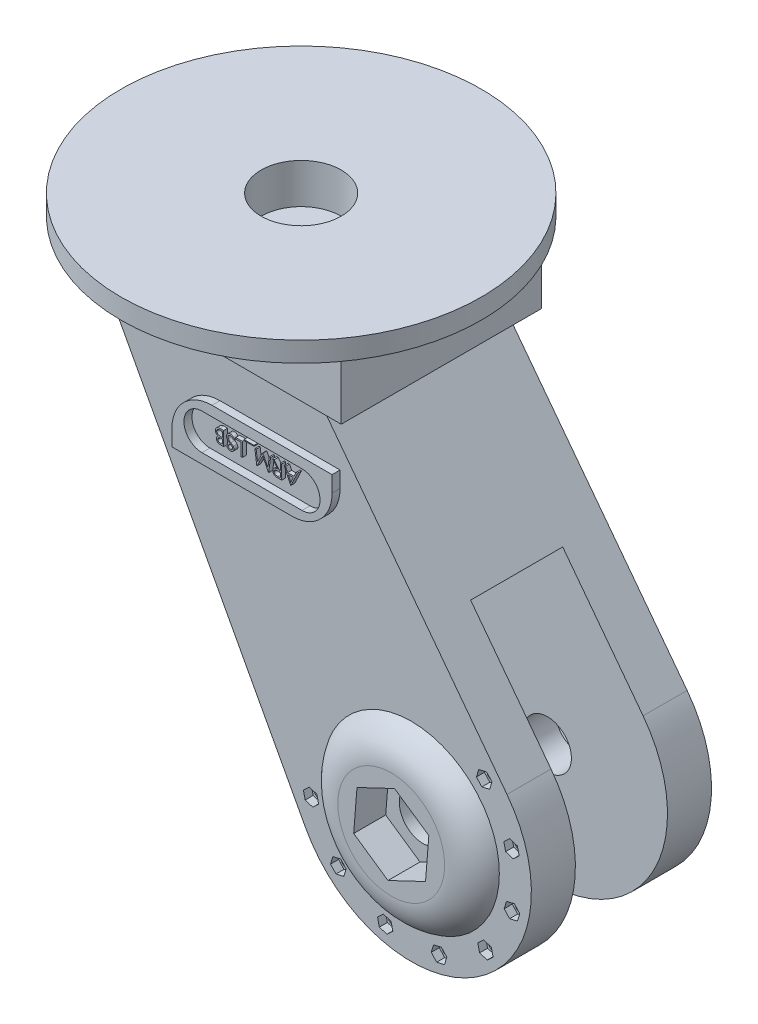
SolidWorks part; units mm, degrees
ref_plane "Ön Düzlem" through (0, 0, 0) normal (0, 0, 1) x (1, 0, 0)
ref_plane "Üst Düzlem" through (0, 0, 0) normal (0, 1, 0) x (1, 0, 0)
ref_plane "Sağ Düzlem" through (0, 0, 0) normal (1, 0, 0) x (0, 0, -1)
sketch "Sketch1" plane through (0, 0, 0) normal (0, 1, 0) x (1, 0, 0)
  circle A0 centre (0, 0) radius 45
  dimension "D1" = 90
extrude "Boss-Extrude1" add sketch "Sketch1" along normal blind 5
sketch "Sketch2" plane through (0, 5, 0) normal (0, 1, 0) x (1, 0, 0)
  line L1 (-35, 25) -> (35, 25)
  line L2 (-35, 25) -> (-35, -25)
  line L3 (-35, -25) -> (35, -25)
  line L4 (35, 25) -> (35, -25)
  line L5 (-35, 25) -> (35, -25) construction
  line L6 (-35, -25) -> (35, 25) construction
  point P0 (0, 0)
  dimension "D1" = 70
  dimension "D2" = 50
extrude "Boss-Extrude2" add sketch "Sketch2" along normal blind 15
sketch "Sketch3" plane through (0, 0, 0) normal (0, 0, 1) x (1, 0, 0)
  line L0 (-45, 0) -> (45, 0) construction
  line L1 (-27, 20) -> (-73.907, 81.8767)
  line L2 (-35, 20) -> (35, 20) construction
  line L3 (-27, 20) -> (27, 20)
  line L4 (27, 20) -> (-23.5684, 114.1904)
  arc A0 (-23.5684, 114.1904) -> (-73.907, 81.8767) centre (-50, 100) ccw
  dimension "D1" = 60
  dimension "D2" = 100
  dimension "D3" = 50
  dimension "D4" = 8
  dimension "D5" = 8
extrude "Boss-Extrude3" add sketch "Sketch3" along normal mid plane 45
sketch "Sketch4" plane through (0, 0, 22.5) normal (0, 0, 1) x (1, 0, 0)
  circle A0 centre (-50, 100) radius 22
  dimension "D1" = 44
extrude "Boss-Extrude4" add sketch "Sketch4" along normal blind 5
fillet "Fillet1" radius 10 1 edges at (-28, 100, 27.5)
sketch "Sketch5" plane through (0, 0, 27.5) normal (0, 0, 1) x (1, 0, 0)
  line L1 (-50.8234, 89.6404) -> (-41.44, 94.1071)
  line L2 (-41.44, 94.1071) -> (-40.6166, 104.4667)
  line L3 (-40.6166, 104.4667) -> (-49.1766, 110.3596)
  line L4 (-49.1766, 110.3596) -> (-58.56, 105.8929)
  line L5 (-58.56, 105.8929) -> (-59.3834, 95.5333)
  line L6 (-59.3834, 95.5333) -> (-50.8234, 89.6404)
  circle A0 centre (-50, 100) radius 9 construction
  dimension "D1" = 18
extrude "Cut-Extrude1" cut sketch "Sketch5" against normal blind 8
sketch "Sketch6" plane through (29.294, 15.7272, 0) normal (0.8811, 0.473, 0) x (0, 0, -1)
  line L0 (-22.5, 111.7562) -> (22.5, 111.7562) construction
  line L1 (-11.5, 149.2562) -> (11.5, 149.2562)
  line L2 (-11.5, 149.2562) -> (-11.5, 74.2562)
  line L3 (-11.5, 74.2562) -> (11.5, 74.2562)
  line L4 (11.5, 149.2562) -> (11.5, 74.2562)
  line L5 (-11.5, 149.2562) -> (11.5, 74.2562) construction
  line L6 (-11.5, 74.2562) -> (11.5, 149.2562) construction
  point P0 (0, 111.7562)
  dimension "D1" = 23
  dimension "D2" = 75
extrude "Cut-Extrude2" cut sketch "Sketch6" against normal blind 110
sketch "Sketch7" plane through (0, 0, 19.5) normal (0, 0, 1) x (1, 0, 0)
  circle A0 centre (-50, 100) radius 6
  dimension "D1" = 12
extrude "Cut-Extrude4" cut sketch "Sketch7" against normal blind 20
sketch "Sketch8" plane through (0, 0, 22.5) normal (0, 0, 1) x (1, 0, 0)
  line L1 (-30.4213, 117.0633) -> (-29.8341, 118.9751)
  line L2 (-29.8341, 118.9751) -> (-31.1963, 120.4396)
  line L3 (-31.1963, 120.4396) -> (-33.1456, 119.9922)
  line L4 (-33.1456, 119.9922) -> (-33.7328, 118.0803)
  line L5 (-33.7328, 118.0803) -> (-32.3706, 116.6159)
  line L6 (-32.3706, 116.6159) -> (-30.4213, 117.0633)
  circle A0 centre (-31.7835, 118.5277) radius 1.7321 construction
  circle A1 centre (-50, 100) radius 22 construction
  point P1 (-34.7311, 115.8386)
  dimension "D1" = 4
  dimension "D2" = 3.99
extrude "Cut-Extrude5" cut sketch "Sketch8" against normal blind 2
sketch "Sketch9" plane through (0, 0, 20.5) normal (0, 0, 1) x (1, 0, 0)
  circle A0 centre (-31.7835, 118.5277) radius 1.25
  dimension "D1" = 2.5
extrude "Cut-Extrude6" cut sketch "Sketch9" against normal blind 1
pattern_circular "CirPattern1" count 12 over 360 about axis through (-50, 100, 22.5) along (0, 0, 1) skipping 7, 8, 9, 10 of "Cut-Extrude5", "Cut-Extrude6"
sketch "Sketch10" plane through (0, 0, 22.5) normal (0, 0, 1) x (1, 0, 0)
  line L0 (-50, 100) -> (0, 20) construction
  line L1 (-27, 20) -> (27, 20) construction
  line L3 (-32.2133, 46.5413) -> (7.7867, 46.5413)
  line L4 (-32.2133, 46.5413) -> (-32.2133, 32.5413)
  line L5 (-32.2133, 32.5413) -> (7.7867, 32.5413)
  line L6 (7.7867, 46.5413) -> (7.7867, 32.5413)
  line L7 (-32.2133, 46.5413) -> (7.7867, 32.5413) construction
  line L8 (-32.2133, 32.5413) -> (7.7867, 46.5413) construction
  point P5 (-12.2133, 39.5413)
  dimension "D1" = 14
  dimension "D2" = 40
extrude "Boss-Extrude5" add sketch "Sketch10" along normal blind 2
sketch "Sketch11" plane through (0, 0, 24.5) normal (0, 0, 1) x (1, 0, 0)
  line L0 (-24.7133, 39.5413) -> (0.2867, 39.5413) construction
  line L1 (-24.7133, 44.0413) -> (0.2867, 44.0413)
  line L2 (-24.7133, 35.0413) -> (0.2867, 35.0413)
  line L3 (-32.2133, 46.5413) -> (-32.2133, 32.5413) construction
  line L4 (7.7867, 32.5413) -> (7.7867, 46.5413) construction
  line L5 (7.7867, 46.5413) -> (-32.2133, 46.5413) construction
  line L6 (-32.2133, 32.5413) -> (7.7867, 32.5413) construction
  arc A0 (-24.7133, 44.0413) -> (-24.7133, 35.0413) centre (-24.7133, 39.5413) ccw
  arc A1 (0.2867, 35.0413) -> (0.2867, 44.0413) centre (0.2867, 39.5413) ccw
  point P2 (-12.2133, 39.5413)
  point P7 (-32.2133, 39.5413)
  point P10 (7.7867, 39.5413)
  dimension "D1" = 7.5
  dimension "D2" = 7.5
  dimension "D3" = 2.5
  dimension "D4" = 2.5
extrude "Cut-Extrude7" cut sketch "Sketch11" against normal blind 2
fillet "Fillet2" radius 10 2 edges at (7.7867, 32.5413, 23.5) (-32.2133, 46.5413, 23.5)
ref_plane "Plane1" through (0, 0, 0) normal (0, 0, -1) x (-1, 0, 0)
mirror "Mirror1" about plane through (0, 0, 0) normal (0, 0, -1) of "Fillet2", "Cut-Extrude7", "Boss-Extrude5", "CirPattern1", "Cut-Extrude6", "Cut-Extrude5", "Cut-Extrude2", "Cut-Extrude4", "Cut-Extrude1", "Fillet1", "Boss-Extrude4"
sketch "Sketch14" plane through (0, 0, -22.5) normal (0, 0, -1) x (-1, 0, 0)
  text T0 "ARM ROBOT"
extrude "Boss-Extrude6" add sketch "Sketch14" along normal blind 1
sketch "Sketch15" plane through (0, 0, 22.5) normal (0, 0, 1) x (1, 0, 0)
  line L0 (0.2867, 44.0413) -> (-24.7133, 44.0413) construction
  text T0 "ARM_LSB"
  dimension "D1" = 6.5
extrude "Boss-Extrude7" add sketch "Sketch15" along normal blind 1
sketch "Sketch16" plane through (35, 0, 0) normal (1, 0, 0) x (0, 0, -1)
  line L0 (-18.5, 12.5) -> (18.5, 12.5) construction
  line L1 (-18.5, 16.5) -> (18.5, 16.5)
  line L2 (-18.5, 8.5) -> (18.5, 8.5)
  line L3 (-25, 20) -> (-25, 5) construction
  line L4 (25, 20) -> (25, 5) construction
  line L5 (-22.5, 20) -> (22.5, 20) construction
  line L6 (-25, 5) -> (25, 5) construction
  arc A0 (-18.5, 16.5) -> (-18.5, 8.5) centre (-18.5, 12.5) ccw
  arc A1 (18.5, 8.5) -> (18.5, 16.5) centre (18.5, 12.5) ccw
  point P2 (0, 12.5)
  point P7 (-25, 12.5)
  point P10 (25, 12.5)
  dimension "D1" = 6.5
  dimension "D2" = 6.5
  dimension "D3" = 3.5
  dimension "D4" = 3.5
extrude "Cut-Extrude8" cut sketch "Sketch16" against normal blind 1
sketch "Sketch17" plane through (34, 0, 0) normal (1, 0, 0) x (0, 0, -1)
  text T0 "DO NOT TOUCH"
extrude "Boss-Extrude8" add sketch "Sketch17" along normal blind 1
sketch "Sketch18" plane through (0, 0, 0) normal (0, -1, 0) x (1, 0, 0)
  circle A0 centre (0, 0) radius 10
  dimension "D1" = 20
extrude "Cut-Extrude9" cut sketch "Sketch18" against normal blind 10
sketch "Sketch19" plane through (0, 0, 0) normal (0, 0, 1) x (1, 0, 0)
  point P0 (-50, 100)
move or copy body "Body-Move/Copy1" bodies to move or copy 119 copy no translate (50, -100, 0)
move or copy body "Body-Move/Copy2" bodies to move or copy 120 copy no rotation origin (0, 0, 0) rotation axis (1, 0, 0) rotation angle 180
move or copy body "Body-Move/Copy3" bodies to move or copy 121 copy no rotation origin (0, 0, 0) rotation axis (0, 1, 0) rotation angle 180
